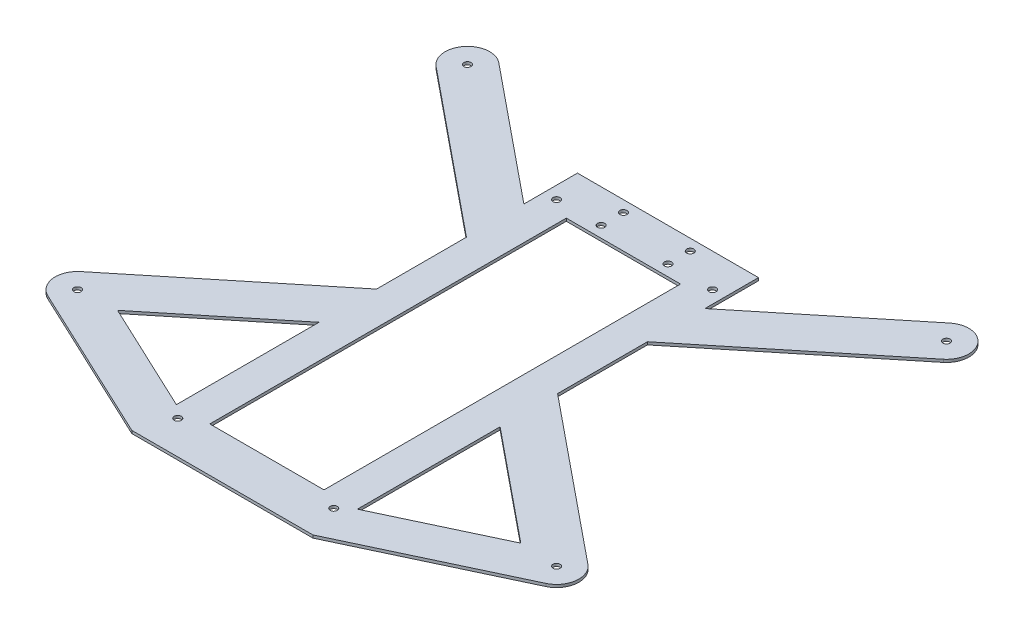
SolidWorks part; units mm, degrees
ref_plane "Front Plane" through (0, 0, 0) normal (0, 0, 1) x (1, 0, 0)
ref_plane "Top Plane" through (0, 0, 0) normal (0, 1, 0) x (1, 0, 0)
ref_plane "Right Plane" through (0, 0, 0) normal (1, 0, 0) x (0, 0, -1)
sketch "Sketch2" plane through (0, 0, 0) normal (0, 1, 0) x (1, 0, 0)
  line L0 (-136.525, 111.125) -> (136.525, -111.125) construction
  line L1 (-128.5079, 120.9746) -> (-51.5937, 58.3701)
  line L2 (-144.5421, 101.2754) -> (-51.5937, 25.6197)
  line L3 (-136.525, -111.125) -> (136.525, 111.125) construction
  line L4 (-144.5421, -101.2754) -> (-51.5937, -25.6197)
  line L5 (-114.9237, -109.9177) -> (-51.5937, -58.3701)
  line L7 (-32.5437, -139.7) -> (32.5437, -139.7)
  line L8 (-32.5437, -139.7) -> (-32.5437, 63.5)
  line L9 (-32.5437, 63.5) -> (32.5437, 63.5)
  line L10 (32.5437, -139.7) -> (32.5437, 63.5)
  line L11 (-32.5437, -139.7) -> (32.5437, 63.5) construction
  line L12 (-32.5437, 63.5) -> (32.5437, -139.7) construction
  line L16 (51.5937, -58.3701) -> (114.9237, -109.9177)
  line L18 (-51.5937, -58.3701) -> (-51.5937, -165.1)
  line L19 (-51.5937, -165.1) -> (51.5937, -165.1)
  line L20 (51.5937, 58.3701) -> (128.5079, 120.9746)
  line L21 (51.5937, 25.6197) -> (144.5421, 101.2754)
  line L22 (51.5937, -25.6197) -> (144.5421, -101.2754)
  line L23 (-51.5937, 58.3701) -> (-51.5937, 88.9)
  line L24 (51.5937, -139.7) -> (51.5937, -58.3701)
  line L25 (51.5937, -25.6197) -> (51.5937, 25.6197)
  line L26 (-51.5937, -25.6197) -> (-51.5937, 25.6197)
  line L27 (-51.5937, 88.9) -> (51.5938, 88.9)
  line L28 (51.5938, 88.9) -> (51.5937, 58.3701)
  line L29 (51.5937, -165.1) -> (141.9296, -122.6176)
  line L30 (114.9237, -109.9177) -> (51.5937, -139.7)
  line L31 (-141.9296, -122.6176) -> (-51.5937, -165.1)
  line L32 (-51.5937, -139.7) -> (-114.9237, -109.9177)
  arc A0 (-128.5079, 120.9746) -> (-144.5421, 101.2754) centre (-136.525, 111.125) ccw
  arc A1 (141.9296, -122.6176) -> (144.5421, -101.2754) centre (136.525, -111.125) ccw
  arc A2 (-144.5421, -101.2754) -> (-141.9296, -122.6176) centre (-136.525, -111.125) ccw
  arc A3 (144.5421, 101.2754) -> (128.5079, 120.9746) centre (136.525, 111.125) ccw
  circle A4 centre (-136.525, 111.125) radius 2.032
  circle A5 centre (136.525, 111.125) radius 2.032
  circle A6 centre (136.525, -111.125) radius 2.032
  circle A7 centre (-136.525, -111.125) radius 2.032
  point P2 (0, 0)
  point P9 (0, 0)
  point P13 (-51.5937, -58.3701)
  point P18 (0, -38.1)
  point P39 (0, 0)
  point P42 (0, 0)
  point P44 (-51.5937, -25.6197)
  point P45 (0, 0)
  point P46 (0, 0)
  dimension "D3" = 12.7
  dimension "D9" = 4.064
  dimension "D1" = 273.05
  dimension "D2" = 222.25
  dimension "D4" = 65.0875
  dimension "D5" = 63.5
  dimension "D6" = 139.7
  dimension "D8" = 25.4
  dimension "D10" = 19.05
  dimension "D7" = 19.05
  dimension "D11" = 25.4
  dimension "D12" = 22.9852
extrude "Boss-Extrude1" add sketch "Sketch2" along normal mid plane 1.5875 contours L21 A3 L20 L1 A0 L2 L26 L4 A2 L5 L16 A1 L22 L25 L10 L7 L8 L9 region at (-92.673, 0, -86.4508)
sketch "Sketch3" plane through (0, -0.7937, 0) normal (0, -1, 0) x (1, 0, 0)
  line L2 (44.45, -69.85) -> (51.5938, -69.85) construction
  line L4 (-44.45, -69.85) -> (-51.5937, -69.85) construction
  line L6 (-51.5937, -58.3701) -> (-51.5937, -88.9) construction
  line L7 (51.5938, -88.9) -> (51.5938, -58.3701) construction
  circle A2 centre (44.45, 146.05) radius 2.032
  circle A3 centre (-44.45, 146.05) radius 2.032
  circle A4 centre (44.45, -69.85) radius 2.032
  circle A5 centre (-44.45, -69.85) radius 2.032
  circle A6 centre (-19.05, -69.85) radius 2.032
  circle A7 centre (19.05, -69.85) radius 2.032
  circle A8 centre (-19.05, -82.55) radius 2.032
  circle A9 centre (19.05, -82.55) radius 2.032
  point P21 (0, 0)
  point P22 (0, 0)
  point P24 (-31.964, -69.85)
  point P25 (0, 0)
  point P26 (0, 0)
  dimension "D3" = 4.064
  dimension "D1" = 25.4
  dimension "D2" = 12.7
  dimension "D4" = 25.4
extrude "Cut-Extrude1" cut sketch "Sketch3" against normal through all
